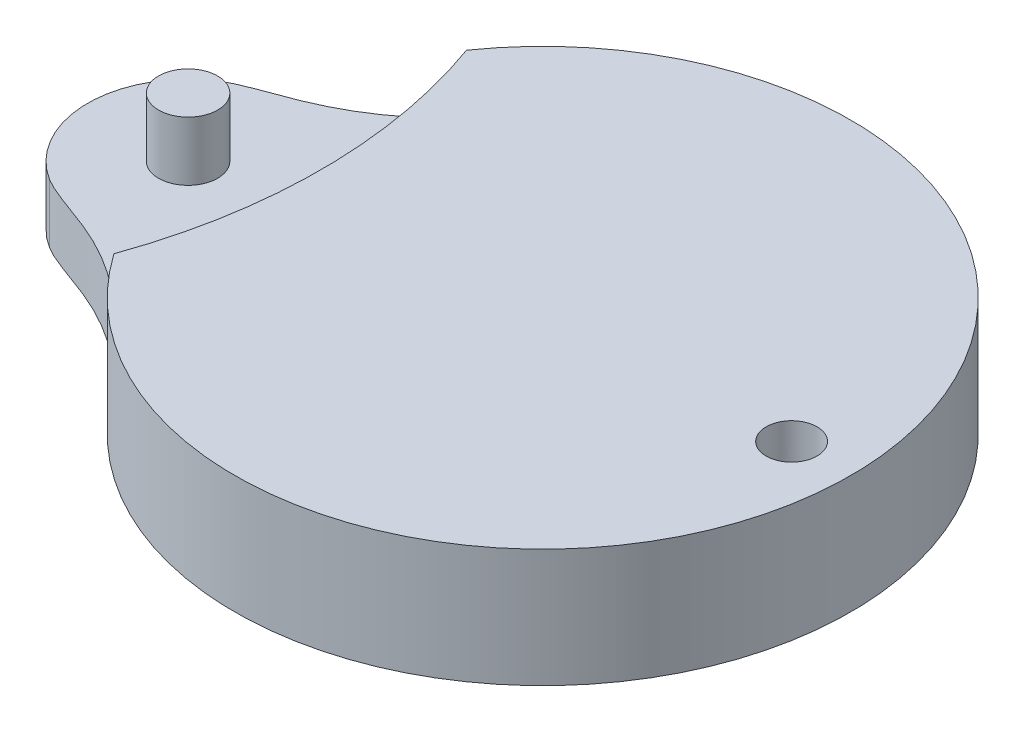
SolidWorks part; units mm, degrees
ref_plane "Front Plane" through (0, 0, 0) normal (0, 0, 1) x (1, 0, 0)
ref_plane "Top Plane" through (0, 0, 0) normal (0, 1, 0) x (1, 0, 0)
ref_plane "Right Plane" through (0, 0, 0) normal (1, 0, 0) x (0, 0, -1)
sketch "Sketch2" plane through (0, 0, 0) normal (0, 1, 0) x (1, 0, 0)
  line L0 (0, 0) -> (62.7561, 0) construction
  line L1 (62.7561, 0) -> (36.9552, 15.3073) construction
  line L2 (36.9552, 15.3073) -> (0, 0) construction
  line L3 (36.9552, 15.3073) -> (30.2627, 12.5352) construction
  line L4 (38.065, 12.6281) -> (31.3724, 9.856)
  line L5 (35.8454, 17.9866) -> (29.1529, 15.2145)
  circle A0 centre (36.9552, 15.3073) radius 2.5
  arc A1 (38.065, 12.6281) -> (35.8454, 17.9866) centre (36.9552, 15.3073) ccw
  arc A2 (29.1529, 15.2145) -> (31.3724, 9.856) centre (30.2627, 12.5352) ccw
  circle A3 centre (62.7561, 0) radius 30
  circle A4 centre (0, 0) radius 40
  circle A5 centre (0, 0) radius 32.7561
  circle A6 centre (62.7561, 0) radius 26.4496
  arc A7 (41.3963, 14.9112) -> (41.3963, -14.9112) centre (62.7561, 0) cw
  arc A8 (41.3963, 14.9112) -> (41.3963, -14.9112) centre (0, 0) cw
  circle A9 centre (32.7561, 0) radius 2.5
  circle A10 centre (32.7561, 0) radius 8.5
  circle A11 centre (83.8056, 0) radius 2.15
  spline S0 degree 3 poles (28.2252, 7.1918) (30.8164, 8.8242) (35.6101, 8.9353) (41.3963, 14.9112) knots 0 0 0 0 1 1 1 1
  spline S1 degree 3 poles (28.2252, -7.1918) (30.8164, -8.8242) (35.6101, -8.9353) (41.3963, -14.9112) knots 0 0 0 0 1 1 1 1
  point P3 (33.6089, 13.9213)
  point P15 (38.552, 10.665)
  point P23 (88.8056, 0)
  dimension "D4" = 5
  dimension "D5" = 2.9
  dimension "D10" = 4.3
  dimension "D1" = 22.5
  dimension "D2" = 40
  dimension "D3" = 30
  dimension "D6" = 2
  dimension "D7" = 0.4
  dimension "D8" = 4
  dimension "D9" = 6
  dimension "D11" = 5
extrude "Boss-Extrude2" add sketch "Sketch2" along normal blind 5 contours A7 A8 | A6 S1 A8 S0 A4 A10 | S0 A4 A6 | S0 A3 A10 A6 A4 | S0 A5 A10 A3 | A3 A10 A5 A9 | A5 A10 A9 | S0 A10 A5 | A5 A9 | A3 A9 A5 | A3 A9 | A5 A9 A3 | A5 A10 A3 A9 | A3 A10 A6 A9 | A5 S1 A3 A10 | A10 S1 A5 | A3 S1 A4 A6 A10 | A10 A6 A4 | A4 S1 A6 | A6 A10 A4 | A4 A10 | A10 A4 A6 region at (38.8989, 0, -12.0929) region at (36.5196, 0, -9.4854) region at (33.2395, 0, -8.9016) region at (41.4813, 0, 0) region at (38.5456, 0, -7.7285) region at (35.6354, 0, -7.8122) region at (32.7873, 0, -6.4801) region at (31.1919, 0, -8.4105) region at (40.4456, 0, 0) region at (38.1402, 0, 0) region at (64.2598, 0, 0) region at (33.2395, 0, 8.9016) region at (36.5196, 0, 9.4854) region at (38.8989, 0, 12.0929) region at (33.8356, 0, 0) region at (32.7587, 0, -1.8747) region at (28.6877, 0, 0) region at (38.5456, 0, 7.7285) region at (32.7873, 0, 6.4801) region at (31.1919, 0, 8.4105) region at (31.678, 0, 0) region at (32.7587, 0, 1.8747)
extrude "Boss-Extrude3" add sketch "Sketch2<4>" along normal blind 10 contours A5 A9 | A5 A9 A3 | A3 A9 | A3 A9 A5 | A7 A8 region at (33.8356, 0, 0) region at (32.7587, 0, -1.8747) region at (31.678, 0, 0) region at (32.7587, 0, 1.8747)
sketch "Sketch2<4>" plane through (0, 0, 0) normal (0, 1, 0) x (1, 0, 0) same geometry as "Sketch2"
extrude "Cut-Extrude1" cut sketch "Sketch2<5>" along direction (0, -1, 0) on the side of the normal up to surface (10 mm away) contours A11 region at (83.8056, 0, 0) up to face at (66.4028, 10, 0)
sketch "Sketch2<5>" plane through (0, 0, 0) normal (0, 1, 0) x (1, 0, 0) same geometry as "Sketch2"
equation "\"angle\"= 22.5"
equation "\"driveR\"= 40"
equation "\"D1@Sketch2\"=\"angle\""
equation "\"D2@Sketch2\"=\"driveR\""
equation "\"wheelR\"= 30"
equation "\"D3@Sketch2\"=\"wheelR\""
equation "\"pin\"= 5"
equation "\"D4@Sketch2\"=\"pin\""
equation "\"D5@Sketch2\"=(\"pin\"/2)+\"tol\""
equation "\"tol\"= 0.4"
equation "\"D7@Sketch2\"=\"tol\""
